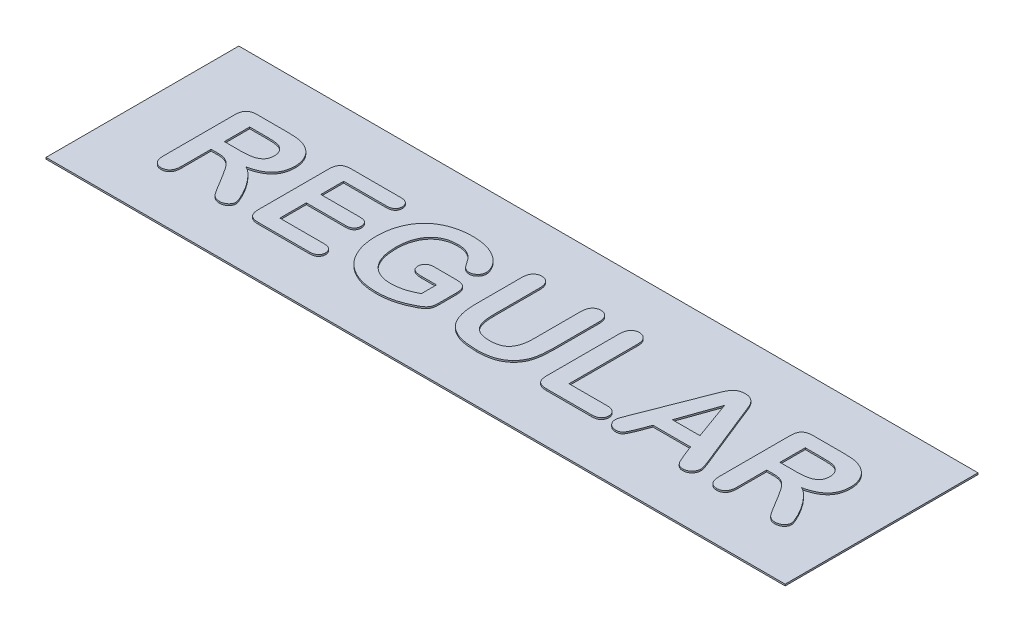
SolidWorks part; units mm, degrees
ref_plane "Front Plane" through (0, 0, 0) normal (0, 0, 1) x (1, 0, 0)
ref_plane "Top Plane" through (0, 0, 0) normal (0, 1, 0) x (1, 0, 0)
ref_plane "Right Plane" through (0, 0, 0) normal (1, 0, 0) x (0, 0, -1)
sketch "Sketch1" plane through (0, 0, 0) normal (0, 1, 0) x (1, 0, 0)
  line L1 (0, 0) -> (46, 0)
  line L2 (0, 0) -> (0, 12)
  line L3 (0, 12) -> (46, 12)
  line L4 (46, 0) -> (46, 12)
  line L5 (5.2055, 5.475) -> (4.8, 5.475)
  line L6 (4.8, 5.475) -> (4.8, 3.6328)
  line L7 (3.675, 3.6352) -> (3.675, 8.0613)
  line L8 (4.3805, 8.775) -> (6.2508, 8.775)
  line L9 (7.0348, 3.6645) -> (6.5637, 4.4391)
  line L10 (5.8688, 7.875) -> (4.8, 7.875)
  line L11 (4.8, 7.875) -> (4.8, 6.3)
  line L12 (4.8, 6.3) -> (5.8371, 6.3)
  line L13 (13.2961, 7.875) -> (10.65, 7.875)
  line L14 (10.65, 7.875) -> (10.65, 6.45)
  line L15 (10.65, 6.45) -> (13.0863, 6.45)
  line L16 (13.0863, 5.55) -> (10.65, 5.55)
  line L17 (10.65, 5.55) -> (10.65, 3.9)
  line L18 (10.65, 3.9) -> (13.3875, 3.9)
  line L19 (13.3875, 3) -> (10.2141, 3)
  line L20 (9.525, 3.7172) -> (9.525, 8.0578)
  line L21 (10.2141, 8.775) -> (13.2961, 8.775)
  line L22 (20.175, 5.373) -> (20.175, 4.2633)
  line L23 (19.125, 4.2352) -> (19.125, 5.175)
  line L24 (19.125, 5.175) -> (18.2063, 5.175)
  line L25 (18.0551, 6.075) -> (19.3828, 6.075)
  line L26 (21.375, 5.4223) -> (21.375, 8.2125)
  line L27 (22.5, 8.2078) -> (22.5, 5.3355)
  line L28 (25.05, 5.3109) -> (25.05, 8.2078)
  line L29 (26.175, 8.2102) -> (26.175, 5.4094)
  line L30 (28.575, 8.2102) -> (28.575, 3.975)
  line L31 (28.575, 3.975) -> (30.9563, 3.975)
  line L32 (30.9563, 3) -> (28.1391, 3)
  line L33 (27.45, 3.723) -> (27.45, 8.2102)
  line L34 (36.034, 3.6504) -> (35.7598, 4.35)
  line L35 (35.7598, 4.35) -> (33.4266, 4.35)
  line L36 (33.4266, 4.35) -> (33.1523, 3.6352)
  line L37 (32.1188, 4.0535) -> (33.5871, 7.8211)
  line L38 (35.5992, 7.8281) -> (37.0992, 4.0852)
  line L39 (33.7313, 5.25) -> (35.4469, 5.25)
  line L40 (35.4469, 5.25) -> (34.5809, 7.65)
  line L41 (34.5809, 7.65) -> (33.7313, 5.25)
  line L42 (39.7805, 5.475) -> (39.375, 5.475)
  line L43 (39.375, 5.475) -> (39.375, 3.6328)
  line L44 (38.25, 3.6352) -> (38.25, 8.0613)
  line L45 (38.9555, 8.775) -> (40.8258, 8.775)
  line L46 (41.6098, 3.6645) -> (41.1387, 4.4391)
  line L47 (40.4438, 7.875) -> (39.375, 7.875)
  line L48 (39.375, 7.875) -> (39.375, 6.3)
  line L49 (39.375, 6.3) -> (40.4121, 6.3)
  spline S0 degree 3 poles (4.8, 3.6328) (4.7999, 3.5272) (4.7879, 3.375) (4.7182, 3.197) (4.6493, 3.0961) (4.564, 3.0196) (4.4319, 2.9442) (4.3168, 2.9243) (4.2398, 2.925) knots 0 0 0 0 0.311508 0.440094 0.557122 0.666708 0.7735 1 1 1 1
  spline S1 degree 3 poles (4.2398, 2.925) (4.1589, 2.9256) (4.0377, 2.9438) (3.9015, 3.0239) (3.8176, 3.104) (3.7526, 3.2075) (3.6889, 3.384) (3.6748, 3.532) (3.675, 3.6352) knots 0 0 0 0 0.237649 0.345821 0.456134 0.572351 0.698802 1 1 1 1
  spline S2 degree 3 poles (3.675, 8.0613) (3.6753, 8.1703) (3.6892, 8.3262) (3.762, 8.508) (3.8371, 8.6104) (3.9383, 8.6867) (4.1178, 8.7615) (4.2728, 8.7744) (4.3805, 8.775) knots 0 0 0 0 0.28252 0.397354 0.501854 0.606159 0.72046 1 1 1 1
  spline S3 degree 3 poles (6.2508, 8.775) (6.3703, 8.7736) (6.5433, 8.7731) (6.7639, 8.7561) (6.9102, 8.7412) (7.046, 8.7212) (7.2135, 8.6801) (7.3335, 8.6381) (7.4086, 8.6016) knots 0 0 0 0 0.303939 0.439345 0.562157 0.677737 0.788039 1 1 1 1
  spline S4 degree 3 poles (7.4086, 8.6016) (7.4991, 8.5639) (7.6296, 8.4944) (7.7877, 8.3774) (7.8966, 8.2771) (7.9967, 8.168) (8.082, 8.0471) (8.1565, 7.9192) (8.2174, 7.7827) (8.2648, 7.6401) (8.3134, 7.4427) (8.3237, 7.2894) (8.325, 7.1871) knots 0 0 0 0 0.164226 0.246594 0.329087 0.412065 0.49419 0.576621 0.659854 0.744124 0.828291 1 1 1 1
  spline S5 degree 3 poles (8.325, 7.1871) (8.3254, 7.0848) (8.3139, 6.9345) (8.2758, 6.7415) (8.2368, 6.6075) (8.1828, 6.4825) (8.1201, 6.3651) (8.0452, 6.2557) (7.9583, 6.1548) (7.859, 6.0622) (7.7489, 5.9759) (7.6272, 5.8962) (7.4927, 5.825) (7.3467, 5.7602) (7.1298, 5.6829) (6.9591, 5.6346) (6.8402, 5.6109) knots 0 0 0 0 0.128839 0.189023 0.247528 0.304161 0.360053 0.41489 0.470686 0.527397 0.585541 0.64665 0.710237 0.776949 0.847579 1 1 1 1
  spline S6 degree 3 poles (6.8402, 5.6109) (6.95, 5.5551) (7.1064, 5.4478) (7.3009, 5.2769) (7.4427, 5.1255) (7.5805, 4.9639) (7.7135, 4.7965) (7.8376, 4.623) (7.9519, 4.4462) (8.0577, 4.2725) (8.1518, 4.1049) (8.2325, 3.9455) (8.3011, 3.7975) (8.3556, 3.6653) (8.4022, 3.5327) (8.4257, 3.4432) (8.4281, 3.3902) knots 0 0 0 0 0.131919 0.20297 0.277761 0.354539 0.431015 0.507401 0.583515 0.657132 0.725887 0.789877 0.849017 0.901145 0.943344 1 1 1 1
  spline S7 degree 3 poles (8.4281, 3.3902) (8.4277, 3.3094) (8.3904, 3.2104) (8.3156, 3.1119) (8.2694, 3.0637) (8.215, 3.0233) (8.1552, 2.9878) (8.0895, 2.9596) (7.992, 2.9327) (7.915, 2.9236) (7.8621, 2.925) knots 0 0 0 0 0.295221 0.376756 0.457519 0.541081 0.626619 0.714698 0.804851 1 1 1 1
  spline S8 degree 3 poles (7.8621, 2.925) (7.8008, 2.9243) (7.7115, 2.9361) (7.6005, 2.9738) (7.5047, 3.0285) (7.3992, 3.1182) (7.3097, 3.2288) (7.2407, 3.3333) (7.1538, 3.472) (7.0824, 3.5831) (7.0348, 3.6645) knots 0 0 0 0 0.156736 0.228882 0.298752 0.437996 0.580828 0.661577 0.758723 1 1 1 1
  spline S9 degree 3 poles (6.5637, 4.4391) (6.4881, 4.566) (6.3792, 4.7452) (6.224, 4.9575) (6.1215, 5.0838) (6.0218, 5.1892) (5.9224, 5.2759) (5.8207, 5.3431) (5.7172, 5.3958) (5.606, 5.4322) (5.4359, 5.468) (5.2998, 5.4751) (5.2055, 5.475) knots 0 0 0 0 0.244142 0.345681 0.434139 0.512613 0.584888 0.651442 0.713465 0.776088 0.844028 1 1 1 1
  spline S10 degree 3 poles (5.8371, 6.3) (5.9657, 6.3011) (6.1507, 6.3063) (6.385, 6.3372) (6.5361, 6.3681) (6.672, 6.4091) (6.7895, 6.4663) (6.893, 6.5325) (6.9776, 6.6151) (7.0456, 6.7122) (7.1101, 6.8718) (7.1252, 7.0053) (7.125, 7.0969) knots 0 0 0 0 0.22342 0.320583 0.409966 0.491045 0.566273 0.636247 0.703392 0.770177 0.84071 1 1 1 1
  spline S11 degree 3 poles (7.125, 7.0969) (7.1264, 7.1729) (7.1108, 7.2848) (7.0595, 7.4242) (7.0065, 7.5187) (6.941, 7.6052) (6.8336, 7.705) (6.7381, 7.7619) (6.6691, 7.7895) knots 0 0 0 0 0.25825 0.380206 0.503359 0.625641 0.747872 1 1 1 1
  spline S12 degree 3 poles (6.6691, 7.7895) (6.6282, 7.8056) (6.559, 7.8258) (6.4568, 7.8417) (6.3632, 7.8553) (6.2572, 7.8643) (6.0911, 7.8714) (5.9602, 7.8763) (5.8688, 7.875) knots 0 0 0 0 0.163378 0.266297 0.383318 0.514253 0.660795 1 1 1 1
  spline S13 degree 3 poles (13.0863, 6.45) (13.165, 6.448) (13.2797, 6.4406) (13.413, 6.3851) (13.4894, 6.3307) (13.5481, 6.2631) (13.6073, 6.1576) (13.6206, 6.0649) (13.6207, 6.0035) knots 0 0 0 0 0.301571 0.427298 0.5443 0.654763 0.765066 1 1 1 1
  spline S14 degree 3 poles (13.6207, 6.0035) (13.6212, 5.9418) (13.6062, 5.8498) (13.5492, 5.7424) (13.4911, 5.6733) (13.4153, 5.6169) (13.2815, 5.56) (13.1659, 5.5514) (13.0863, 5.55) knots 0 0 0 0 0.233451 0.343652 0.455654 0.571599 0.697115 1 1 1 1
  spline S15 degree 3 poles (13.3875, 3.9) (13.4684, 3.8977) (13.5872, 3.8909) (13.7253, 3.8341) (13.8058, 3.7793) (13.8694, 3.7119) (13.9293, 3.6031) (13.947, 3.5098) (13.9453, 3.4465) knots 0 0 0 0 0.301115 0.428958 0.546002 0.658095 0.767064 1 1 1 1
  spline S16 degree 3 poles (13.9453, 3.4465) (13.9475, 3.3849) (13.9286, 3.2943) (13.8691, 3.1879) (13.8058, 3.1208) (13.7255, 3.0656) (13.5864, 3.0118) (13.469, 3.0004) (13.3875, 3) knots 0 0 0 0 0.227881 0.33652 0.449574 0.567623 0.696013 1 1 1 1
  spline S17 degree 3 poles (10.2141, 3) (10.1083, 3.0003) (9.956, 3.0136) (9.78, 3.0883) (9.6806, 3.1649) (9.6088, 3.2688) (9.5369, 3.4512) (9.5273, 3.6084) (9.525, 3.7172) knots 0 0 0 0 0.276681 0.389999 0.493502 0.598427 0.714697 1 1 1 1
  spline S18 degree 3 poles (9.525, 8.0578) (9.5257, 8.1342) (9.5315, 8.2443) (9.562, 8.3814) (9.5938, 8.4682) (9.6345, 8.5446) (9.6872, 8.6092) (9.7503, 8.6623) (9.823, 8.7054) (9.9067, 8.7362) (10.0364, 8.7697) (10.1418, 8.7734) (10.2141, 8.775) knots 0 0 0 0 0.198924 0.285459 0.364561 0.438696 0.509487 0.580148 0.652133 0.728383 0.811204 1 1 1 1
  spline S19 degree 3 poles (13.2961, 8.775) (13.3776, 8.7722) (13.4973, 8.7667) (13.635, 8.709) (13.7147, 8.6547) (13.7747, 8.5864) (13.8368, 8.4818) (13.8503, 8.3887) (13.8504, 8.3273) knots 0 0 0 0 0.306655 0.434289 0.551174 0.662301 0.769708 1 1 1 1
  spline S20 degree 3 poles (13.8504, 8.3273) (13.8508, 8.2646) (13.8362, 8.1703) (13.7754, 8.0627) (13.7146, 7.9942) (13.6352, 7.9396) (13.4966, 7.8843) (13.3779, 7.8771) (13.2961, 7.875) knots 0 0 0 0 0.233121 0.34237 0.452806 0.568964 0.695252 1 1 1 1
  spline S21 degree 3 poles (20.175, 4.2633) (20.1759, 4.1967) (20.1707, 4.1021) (20.1536, 3.984) (20.1348, 3.9103) (20.1083, 3.8442) (20.0739, 3.7819) (20.029, 3.7238) (19.9115, 3.6023) (19.7878, 3.5236) (19.6852, 3.4652) knots 0 0 0 0 0.198985 0.28292 0.356593 0.425796 0.495353 0.568721 0.644737 1 1 1 1
  spline S22 degree 3 poles (19.6852, 3.4652) (19.5166, 3.3747) (19.2621, 3.2551) (18.9184, 3.126) (18.6679, 3.0511) (18.4146, 2.9943) (18.0594, 2.9406) (17.786, 2.9247) (17.6004, 2.925) knots 0 0 0 0 0.263478 0.386936 0.505444 0.623475 0.744343 1 1 1 1
  spline S23 degree 3 poles (17.6004, 2.925) (17.3854, 2.9245) (17.0685, 2.9495) (16.6606, 3.0341) (16.3766, 3.1247) (16.1097, 3.2392) (15.8625, 3.3783) (15.6346, 3.5391) (15.4287, 3.7244) (15.2438, 3.9311) (15.0826, 4.1604) (14.9442, 4.4101) (14.8279, 4.6792) (14.7363, 4.9668) (14.65, 5.3821) (14.6237, 5.7052) (14.625, 5.925) knots 0 0 0 0 0.135047 0.19902 0.261349 0.322032 0.381153 0.439242 0.496944 0.554829 0.613119 0.672668 0.733899 0.797004 0.861988 1 1 1 1
  spline S24 degree 3 poles (14.625, 5.925) (14.6257, 6.1417) (14.6477, 6.4621) (14.7335, 6.8743) (14.8223, 7.1628) (14.9356, 7.4339) (15.0728, 7.685) (15.2346, 7.914) (15.4193, 8.1218) (15.6281, 8.306) (15.8579, 8.4691) (16.11, 8.6071) (16.3825, 8.7224) (16.6744, 8.8134) (17.0996, 8.9034) (17.4325, 8.9244) (17.659, 8.925) knots 0 0 0 0 0.134577 0.198481 0.260901 0.321641 0.380557 0.438135 0.495314 0.552673 0.610589 0.669834 0.730668 0.793927 0.859355 1 1 1 1
  spline S25 degree 3 poles (17.659, 8.925) (17.8439, 8.9253) (18.1149, 8.9087) (18.4608, 8.8418) (18.6955, 8.7739) (18.9102, 8.6903) (19.1064, 8.5986) (19.2804, 8.4945) (19.4321, 8.3796) (19.5654, 8.26) (19.68, 8.1352) (19.7804, 8.0089) (19.8591, 7.878) (19.9202, 7.7499) (19.9817, 7.5956) (19.9995, 7.4775) (20.0016, 7.4027) knots 0 0 0 0 0.181803 0.265915 0.345872 0.421598 0.492186 0.558496 0.620467 0.678916 0.734346 0.78688 0.837189 0.884072 0.92636 1 1 1 1
  spline S26 degree 3 poles (20.0016, 7.4027) (20.0005, 7.3331) (19.9832, 7.2272) (19.9132, 7.1041) (19.8432, 7.023) (19.7595, 6.9553) (19.6334, 6.8876) (19.5265, 6.8685) (19.4555, 6.8695) knots 0 0 0 0 0.24758 0.369504 0.496961 0.624778 0.748468 1 1 1 1
  spline S27 degree 3 poles (19.4555, 6.8695) (19.3727, 6.87) (19.2039, 6.9118) (19.0754, 7.0288) (19.0254, 7.098) knots 0 0 0 0 0.491718 1 1 1 1
  spline S28 degree 3 poles (19.0254, 7.098) (18.961, 7.1998) (18.8656, 7.3403) (18.7389, 7.5103) (18.6557, 7.6112) (18.5716, 7.7003) (18.4736, 7.7758) (18.3648, 7.8466) (18.2416, 7.9089) (18.1039, 7.9629) (17.885, 8.0141) (17.7094, 8.0252) (17.5875, 8.025) knots 0 0 0 0 0.199024 0.280652 0.350356 0.415206 0.48278 0.554254 0.629635 0.710589 0.798302 1 1 1 1
  spline S29 degree 3 poles (17.5875, 8.025) (17.457, 8.0233) (17.2642, 8.0102) (17.0197, 7.9489) (16.8515, 7.8868) (16.6949, 7.8078) (16.5494, 7.7137) (16.4162, 7.6026) (16.2952, 7.4756) (16.1874, 7.3329) (16.0913, 7.176) (16.0112, 7.0025) (15.9432, 6.8156) (15.8911, 6.6154) (15.8379, 6.3286) (15.8266, 6.1053) (15.825, 5.9543) knots 0 0 0 0 0.127642 0.187398 0.245562 0.30236 0.358321 0.41438 0.471299 0.529272 0.588664 0.650598 0.715506 0.782576 0.85237 1 1 1 1
  spline S30 degree 3 poles (15.825, 5.9543) (15.8249, 5.7931) (15.8369, 5.5572) (15.8884, 5.2557) (15.9393, 5.0504) (16.0065, 4.8599) (16.0869, 4.6831) (16.1834, 4.5214) (16.295, 4.3757) (16.4198, 4.2462) (16.5562, 4.1328) (16.705, 4.0372) (16.8658, 3.9598) (17.0374, 3.8986) (17.288, 3.8393) (17.485, 3.8248) (17.6191, 3.825) knots 0 0 0 0 0.153121 0.223462 0.290006 0.353679 0.414896 0.474095 0.532011 0.58865 0.644477 0.700014 0.756062 0.813525 0.872608 1 1 1 1
  spline S31 degree 3 poles (17.6191, 3.825) (17.7524, 3.8252) (17.9498, 3.8383) (18.2071, 3.8819) (18.3923, 3.9299) (18.5752, 3.9891) (18.8227, 4.0844) (19.0044, 4.172) (19.125, 4.2352) knots 0 0 0 0 0.25333 0.375477 0.495851 0.616856 0.741037 1 1 1 1
  spline S32 degree 3 poles (18.2063, 5.175) (18.1087, 5.1727) (17.9713, 5.1856) (17.8033, 5.2262) (17.7053, 5.2705) (17.6281, 5.3321) (17.549, 5.4426) (17.5355, 5.5494) (17.5348, 5.6191) knots 0 0 0 0 0.318178 0.448793 0.562963 0.666395 0.768008 1 1 1 1
  spline S33 degree 3 poles (17.5348, 5.6191) (17.5328, 5.681) (17.5514, 5.7726) (17.6113, 5.8798) (17.6726, 5.9492) (17.7497, 6.0057) (17.8751, 6.0637) (17.9828, 6.0736) (18.0551, 6.075) knots 0 0 0 0 0.238017 0.352116 0.470709 0.592557 0.718731 1 1 1 1
  spline S34 degree 3 poles (19.3828, 6.075) (19.4583, 6.0751) (19.5671, 6.0715) (19.7049, 6.0519) (19.7953, 6.0328) (19.8778, 6.0039) (19.9521, 5.961) (20.0173, 5.9034) (20.0744, 5.8321) (20.1214, 5.744) (20.167, 5.5906) (20.1732, 5.4627) (20.175, 5.373) knots 0 0 0 0 0.182635 0.262813 0.336401 0.405748 0.473492 0.54247 0.615075 0.69328 0.782343 1 1 1 1
  spline S35 degree 3 poles (21.375, 8.2125) (21.3742, 8.3173) (21.3889, 8.4676) (21.4555, 8.6459) (21.524, 8.7482) (21.6078, 8.8281) (21.7404, 8.9043) (21.8545, 8.9269) (21.9316, 8.925) knots 0 0 0 0 0.308193 0.437463 0.554831 0.666785 0.774182 1 1 1 1
  spline S36 degree 3 poles (21.9316, 8.925) (22.011, 8.924) (22.1307, 8.9063) (22.2665, 8.8273) (22.3514, 8.747) (22.4192, 8.6437) (22.4867, 8.4647) (22.5001, 8.3132) (22.5, 8.2078) knots 0 0 0 0 0.231224 0.339606 0.449957 0.566585 0.694004 1 1 1 1
  spline S37 degree 3 poles (22.5, 5.3355) (22.5008, 5.1853) (22.5103, 4.9683) (22.5569, 4.695) (22.6038, 4.5181) (22.6696, 4.3602) (22.7571, 4.2211) (22.8667, 4.1011) (22.9747, 4.0172) (23.072, 3.9617) (23.1529, 3.9252) (23.2404, 3.8932) (23.3358, 3.8697) (23.4369, 3.8491) (23.5858, 3.8308) (23.7013, 3.8235) (23.7809, 3.825) knots 0 0 0 0 0.196282 0.282724 0.361536 0.434661 0.505262 0.574936 0.645832 0.682836 0.720949 0.761601 0.804275 0.848983 0.896299 1 1 1 1
  spline S38 degree 3 poles (23.7809, 3.825) (23.8887, 3.8244) (24.0447, 3.8357) (24.2426, 3.873) (24.372, 3.9145) (24.4896, 3.966) (24.5943, 4.0291) (24.6865, 4.1042) (24.7656, 4.1917) (24.8324, 4.2921) (24.8914, 4.4026) (24.9401, 4.5255) (24.9813, 4.6594) (25.0127, 4.8057) (25.0428, 5.0236) (25.0493, 5.194) (25.05, 5.3109) knots 0 0 0 0 0.143077 0.20704 0.266894 0.323069 0.377047 0.428633 0.480394 0.53303 0.588237 0.646394 0.708228 0.77403 0.84472 1 1 1 1
  spline S39 degree 3 poles (25.05, 8.2078) (25.051, 8.3137) (25.0614, 8.4664) (25.1296, 8.6455) (25.1966, 8.7481) (25.2795, 8.8288) (25.4137, 8.904) (25.5285, 8.9276) (25.6066, 8.925) knots 0 0 0 0 0.310607 0.439089 0.555111 0.665557 0.773287 1 1 1 1
  spline S40 degree 3 poles (25.6066, 8.925) (25.6853, 8.9269) (25.8016, 8.9044) (25.9369, 8.8285) (26.0227, 8.7491) (26.0934, 8.6475) (26.1623, 8.468) (26.1749, 8.3159) (26.175, 8.2102) knots 0 0 0 0 0.227643 0.335773 0.446498 0.563795 0.691995 1 1 1 1
  spline S41 degree 3 poles (26.175, 5.4094) (26.1737, 5.2002) (26.1636, 4.899) (26.1079, 4.5194) (26.0543, 4.2725) (25.9763, 4.0461) (25.8329, 3.7644) (25.6829, 3.578) (25.5691, 3.4664) knots 0 0 0 0 0.29964 0.4302 0.548894 0.660835 0.771868 1 1 1 1
  spline S42 degree 3 poles (25.5691, 3.4664) (25.4657, 3.373) (25.2945, 3.2506) (25.0429, 3.1246) (24.84, 3.0495) (24.622, 2.9935) (24.2991, 2.9395) (24.0461, 2.9248) (23.8723, 2.925) knots 0 0 0 0 0.22915 0.344102 0.462033 0.584228 0.713959 1 1 1 1
  spline S43 degree 3 poles (23.8723, 2.925) (23.6671, 2.9253) (23.3695, 2.9406) (22.9906, 3.0007) (22.7395, 3.0639) (22.5099, 3.1448) (22.304, 3.2494) (22.1172, 3.3696) (21.9542, 3.5133) (21.8121, 3.6769) (21.69, 3.8614) (21.5916, 4.0684) (21.5094, 4.2954) (21.4506, 4.5454) (21.388, 4.9215) (21.377, 5.2182) (21.375, 5.4223) knots 0 0 0 0 0.150122 0.217606 0.28042 0.339375 0.395369 0.449044 0.501509 0.553785 0.607222 0.662835 0.721156 0.783554 0.850474 1 1 1 1
  spline S44 degree 3 poles (30.9563, 3.975) (31.0413, 3.9763) (31.1638, 3.9613) (31.3098, 3.9013) (31.3942, 3.8379) (31.4622, 3.7636) (31.5291, 3.6493) (31.5455, 3.5497) (31.5457, 3.484) knots 0 0 0 0 0.29564 0.422721 0.544076 0.659398 0.770688 1 1 1 1
  spline S45 degree 3 poles (31.5457, 3.484) (31.5459, 3.4175) (31.5294, 3.3171) (31.4628, 3.2027) (31.3957, 3.13) (31.3113, 3.07) (31.1647, 3.0134) (31.0421, 2.9988) (30.9563, 3) knots 0 0 0 0 0.232558 0.344108 0.456772 0.574921 0.701249 1 1 1 1
  spline S46 degree 3 poles (28.1391, 3) (28.0328, 2.9988) (27.8813, 3.0154) (27.7045, 3.0892) (27.606, 3.1673) (27.5334, 3.2714) (27.4621, 3.4554) (27.4522, 3.6134) (27.45, 3.723) knots 0 0 0 0 0.275852 0.38874 0.49248 0.597007 0.713775 1 1 1 1
  spline S47 degree 3 poles (27.45, 8.2102) (27.4499, 8.3151) (27.463, 8.466) (27.5312, 8.6439) (27.5985, 8.7471) (27.6832, 8.8266) (27.8144, 8.9056) (27.9304, 8.9239) (28.0066, 8.925) knots 0 0 0 0 0.308898 0.436927 0.555089 0.666891 0.774722 1 1 1 1
  spline S48 degree 3 poles (28.0066, 8.925) (28.0853, 8.9269) (28.2016, 8.9044) (28.3369, 8.8285) (28.4227, 8.7491) (28.4934, 8.6475) (28.5622, 8.468) (28.5753, 8.316) (28.575, 8.2102) knots 0 0 0 0 0.227639 0.335766 0.446489 0.563783 0.691981 1 1 1 1
  spline S49 degree 3 poles (33.1523, 3.6352) (33.107, 3.5171) (33.0414, 3.3561) (32.9446, 3.1703) (32.8845, 3.0736) (32.8144, 3.0023) (32.6901, 2.9375) (32.5805, 2.9257) (32.5055, 2.925) knots 0 0 0 0 0.364089 0.4988 0.602581 0.690781 0.782793 1 1 1 1
  spline S50 degree 3 poles (32.5055, 2.925) (32.4349, 2.9249) (32.3287, 2.9458) (32.2019, 3.0148) (32.1155, 3.0843) (32.0427, 3.1665) (31.9723, 3.2872) (31.9492, 3.3884) (31.95, 3.4559) knots 0 0 0 0 0.249579 0.37528 0.508208 0.640618 0.762158 1 1 1 1
  spline S51 degree 3 poles (31.95, 3.4559) (31.9494, 3.539) (31.9683, 3.6458) (32.0136, 3.7744) (32.0556, 3.8925) (32.0913, 3.987) (32.1188, 4.0535) knots 0 0 0 0 0.398094 0.514957 0.654391 1 1 1 1
  spline S52 degree 3 poles (33.5871, 7.8211) (33.6092, 7.8809) (33.6471, 7.9734) (33.6956, 8.1037) (33.7371, 8.2105) (33.7794, 8.3174) (33.827, 8.4164) (33.8729, 8.5073) (33.9227, 8.5883) (33.977, 8.6614) (34.0393, 8.7259) (34.1098, 8.7826) (34.187, 8.8338) (34.2741, 8.8749) (34.4075, 8.9157) (34.5152, 8.9248) (34.5891, 8.925) knots 0 0 0 0 0.118107 0.185507 0.257743 0.330515 0.398562 0.461414 0.519309 0.57465 0.629977 0.685071 0.74213 0.801425 0.862829 1 1 1 1
  spline S53 degree 3 poles (34.5891, 8.925) (34.6638, 8.925) (34.7724, 8.9154) (34.9071, 8.8755) (34.9933, 8.8333) (35.0711, 8.7836) (35.1419, 8.7278) (35.2034, 8.6634) (35.2747, 8.5689) (35.3515, 8.4408) (35.4156, 8.3026) (35.4622, 8.181) (35.524, 8.0328) (35.5665, 7.9122) (35.5992, 7.8281) knots 0 0 0 0 0.13864 0.20075 0.259405 0.316084 0.371754 0.426069 0.480846 0.591061 0.702236 0.763048 0.832606 1 1 1 1
  spline S54 degree 3 poles (37.0992, 4.0852) (37.1248, 4.0187) (37.1656, 3.9245) (37.2045, 3.7996) (37.2322, 3.7188) (37.2499, 3.644) (37.2685, 3.5602) (37.2753, 3.5003) (37.275, 3.4629) knots 0 0 0 0 0.32886 0.473133 0.60373 0.722691 0.82773 1 1 1 1
  spline S55 degree 3 poles (37.275, 3.4629) (37.2742, 3.3969) (37.2543, 3.2947) (37.1817, 3.1753) (37.1106, 3.09) (37.0248, 3.0169) (36.8933, 2.9452) (36.7822, 2.9248) (36.7078, 2.925) knots 0 0 0 0 0.230435 0.351645 0.482852 0.615973 0.741252 1 1 1 1
  spline S56 degree 3 poles (36.7078, 2.925) (36.6281, 2.9245) (36.5089, 2.9428) (36.381, 3.0254) (36.3164, 3.0883) (36.2719, 3.1511) (36.2369, 3.2087) (36.2007, 3.2769) (36.131, 3.4245) (36.0789, 3.5517) (36.034, 3.6504) knots 0 0 0 0 0.226524 0.32526 0.423905 0.478175 0.541284 0.613522 0.69508 1 1 1 1
  spline S57 degree 3 poles (39.375, 3.6328) (39.3749, 3.5272) (39.3629, 3.375) (39.2932, 3.197) (39.2243, 3.0961) (39.139, 3.0196) (39.0069, 2.9442) (38.8918, 2.9243) (38.8148, 2.925) knots 0 0 0 0 0.311508 0.440094 0.557122 0.666708 0.7735 1 1 1 1
  spline S58 degree 3 poles (38.8148, 2.925) (38.7339, 2.9256) (38.6127, 2.9438) (38.4765, 3.0239) (38.3926, 3.104) (38.3276, 3.2075) (38.2639, 3.384) (38.2498, 3.532) (38.25, 3.6352) knots 0 0 0 0 0.237649 0.345821 0.456134 0.572351 0.698802 1 1 1 1
  spline S59 degree 3 poles (38.25, 8.0613) (38.2503, 8.1703) (38.2642, 8.3262) (38.337, 8.508) (38.4121, 8.6104) (38.5133, 8.6867) (38.6928, 8.7615) (38.8478, 8.7744) (38.9555, 8.775) knots 0 0 0 0 0.28252 0.397354 0.501854 0.606159 0.72046 1 1 1 1
  spline S60 degree 3 poles (40.8258, 8.775) (40.9453, 8.7736) (41.1183, 8.7731) (41.3389, 8.7561) (41.4852, 8.7412) (41.621, 8.7212) (41.7885, 8.6801) (41.9085, 8.6381) (41.9836, 8.6016) knots 0 0 0 0 0.303939 0.439345 0.562157 0.677737 0.788039 1 1 1 1
  spline S61 degree 3 poles (41.9836, 8.6016) (42.0741, 8.5639) (42.2046, 8.4944) (42.3627, 8.3774) (42.4716, 8.2771) (42.5717, 8.168) (42.657, 8.0471) (42.7315, 7.9192) (42.7924, 7.7827) (42.8398, 7.6401) (42.8884, 7.4427) (42.8987, 7.2894) (42.9, 7.1871) knots 0 0 0 0 0.164226 0.246594 0.329087 0.412065 0.49419 0.576621 0.659854 0.744124 0.828291 1 1 1 1
  spline S62 degree 3 poles (42.9, 7.1871) (42.9004, 7.0848) (42.8889, 6.9345) (42.8508, 6.7415) (42.8118, 6.6075) (42.7578, 6.4825) (42.6951, 6.3651) (42.6202, 6.2557) (42.5333, 6.1548) (42.434, 6.0622) (42.3239, 5.9759) (42.2022, 5.8962) (42.0677, 5.825) (41.9217, 5.7602) (41.7048, 5.6829) (41.5341, 5.6346) (41.4152, 5.6109) knots 0 0 0 0 0.128839 0.189023 0.247528 0.304161 0.360053 0.41489 0.470686 0.527397 0.585541 0.64665 0.710237 0.776949 0.847579 1 1 1 1
  spline S63 degree 3 poles (41.4152, 5.6109) (41.525, 5.5551) (41.6814, 5.4478) (41.8759, 5.2769) (42.0177, 5.1255) (42.1555, 4.9639) (42.2885, 4.7965) (42.4126, 4.623) (42.5269, 4.4462) (42.6327, 4.2725) (42.7268, 4.1049) (42.8075, 3.9455) (42.8761, 3.7975) (42.9306, 3.6653) (42.9772, 3.5327) (43.0007, 3.4432) (43.0031, 3.3902) knots 0 0 0 0 0.131919 0.20297 0.277761 0.354539 0.431015 0.507401 0.583515 0.657132 0.725887 0.789877 0.849017 0.901145 0.943344 1 1 1 1
  spline S64 degree 3 poles (43.0031, 3.3902) (43.0027, 3.3094) (42.9654, 3.2104) (42.8906, 3.1119) (42.8444, 3.0637) (42.79, 3.0233) (42.7302, 2.9878) (42.6645, 2.9596) (42.567, 2.9327) (42.49, 2.9236) (42.4371, 2.925) knots 0 0 0 0 0.295221 0.376756 0.457519 0.541081 0.626619 0.714698 0.804851 1 1 1 1
  spline S65 degree 3 poles (42.4371, 2.925) (42.3758, 2.9243) (42.2865, 2.9361) (42.1755, 2.9738) (42.0797, 3.0285) (41.9742, 3.1182) (41.8847, 3.2288) (41.8157, 3.3333) (41.7288, 3.472) (41.6574, 3.5831) (41.6098, 3.6645) knots 0 0 0 0 0.156736 0.228882 0.298752 0.437996 0.580828 0.661577 0.758723 1 1 1 1
  spline S66 degree 3 poles (41.1387, 4.4391) (41.0631, 4.566) (40.9542, 4.7452) (40.799, 4.9575) (40.6965, 5.0838) (40.5968, 5.1892) (40.4974, 5.2759) (40.3957, 5.3431) (40.2922, 5.3958) (40.181, 5.4322) (40.0109, 5.468) (39.8748, 5.4751) (39.7805, 5.475) knots 0 0 0 0 0.244142 0.345681 0.434139 0.512613 0.584888 0.651442 0.713465 0.776088 0.844028 1 1 1 1
  spline S67 degree 3 poles (40.4121, 6.3) (40.5407, 6.3011) (40.7257, 6.3063) (40.96, 6.3372) (41.1111, 6.3681) (41.247, 6.4091) (41.3645, 6.4663) (41.468, 6.5325) (41.5526, 6.6151) (41.6206, 6.7122) (41.6851, 6.8718) (41.7002, 7.0053) (41.7, 7.0969) knots 0 0 0 0 0.22342 0.320583 0.409966 0.491045 0.566273 0.636247 0.703392 0.770177 0.84071 1 1 1 1
  spline S68 degree 3 poles (41.7, 7.0969) (41.7014, 7.1729) (41.6858, 7.2848) (41.6345, 7.4242) (41.5815, 7.5187) (41.516, 7.6052) (41.4086, 7.705) (41.3131, 7.7619) (41.2441, 7.7895) knots 0 0 0 0 0.25825 0.380206 0.503359 0.625641 0.747872 1 1 1 1
  spline S69 degree 3 poles (41.2441, 7.7895) (41.2032, 7.8056) (41.134, 7.8258) (41.0318, 7.8417) (40.9382, 7.8553) (40.8322, 7.8643) (40.6661, 7.8714) (40.5352, 7.8763) (40.4438, 7.875) knots 0 0 0 0 0.163378 0.266297 0.383318 0.514253 0.660795 1 1 1 1
  dimension "D3" = 12
  dimension "D4" = 46
extrude "Boss-Extrude2" add sketch "Sketch1" against normal blind 0.1 contours L1 L4 L3 L2 S55 S56 L34 L35 L36 S49 S50 S51 L37 S52 S53 L38 S54 L9 S9 L5 L6 S0 S1 L7 S2 L8 S3 S4 S5 S6 S7 S8 S19 S20 L13 L14 L15 S13 S14 L16 L17 L18 S15 S16 L19 S17 L20 S18 | S11 S12 L10 L11 L12 S10 | S9 L9 S8 S7 S6 S5 S4 S3 L8 S2 L7 S1 S0 L6 L5 S12 S11 S10 L12 L11 L10 | S20 S19 L21 S18 L20 S17 L19 S16 S15 L18 L17 L16 S14 S13 L15 L14 L13 | S34 L25 S33 S32 L24 L23 S31 S30 S29 S28 S27 S26 S25 S24 S23 S22 S21 L22 | S43 S42 S41 L29 S40 S39 L28 S38 S37 L27 S36 S35 L26 | S48 S47 L33 S46 L32 S45 S44 L31 L30 | L40 L41 L39 | S56 S55 S54 L38 S53 S52 L37 S51 S50 S49 L36 L35 L34 L41 L40 L39 | S66 L46 S65 S64 S63 S62 S61 S60 L45 S59 L44 S58 S57 L43 L42 S69 S68 S67 L49 L48 L47 | S68 S69 L47 L48 L49 S67 region at (23.0089, 0, -6.0225) region at (5.8518, 0, -6.1068) region at (5.8807, 0, -7.0905) region at (11.2769, 0, -5.8935) region at (20.0933, 0, -4.8182) region at (21.4518, 0, -6.8174) region at (28.503, 0, -6.0926) region at (35.9716, 0, -4.0295) region at (34.5863, 0, -6.05) region at (40.4268, 0, -6.1068) region at (40.4557, 0, -7.0905)
extrude "Boss-Extrude3" add sketch "Sketch1<8>" along normal blind 0.1 separate body contours S9 L9 S8 S7 S6 S5 S4 S3 L8 S2 L7 S1 S0 L6 L5 S12 S11 S10 L12 L11 L10 | S20 S19 L21 S18 L20 S17 L19 S16 S15 L18 L17 L16 S14 S13 L15 L14 L13 | S34 L25 S33 S32 L24 L23 S31 S30 S29 S28 S27 S26 S25 S24 S23 S22 S21 L22 | S43 S42 S41 L29 S40 S39 L28 S38 S37 L27 S36 S35 L26 | S48 S47 L33 S46 L32 S45 S44 L31 L30 | S56 S55 S54 L38 S53 S52 L37 S51 S50 S49 L36 L35 L34 L41 L40 L39 | S66 L46 S65 S64 S63 S62 S61 S60 L45 S59 L44 S58 S57 L43 L42 S69 S68 S67 L49 L48 L47 region at (5.8518, 0, -6.1068) region at (11.2769, 0, -5.8935) region at (20.0933, 0, -4.8182) region at (21.4518, 0, -6.8174) region at (28.503, 0, -6.0926) region at (35.9716, 0, -4.0295) region at (40.4268, 0, -6.1068)
sketch "Sketch1<8>" plane through (0, 0, 0) normal (0, 1, 0) x (1, 0, 0) same geometry as "Sketch1"
sketch "Sketch2" plane through (0, 0, 0) normal (0, 1, 0) x (1, 0, 0)
  line L0 (23, 12) -> (23, 0) construction
  line L1 (0, 12) -> (46, 12) construction
  line L2 (0, 0) -> (46, 0) construction
ref_plane "Plane1" through (23, 0, 0) normal (1, 0, 0) x (0, 0, -1)
